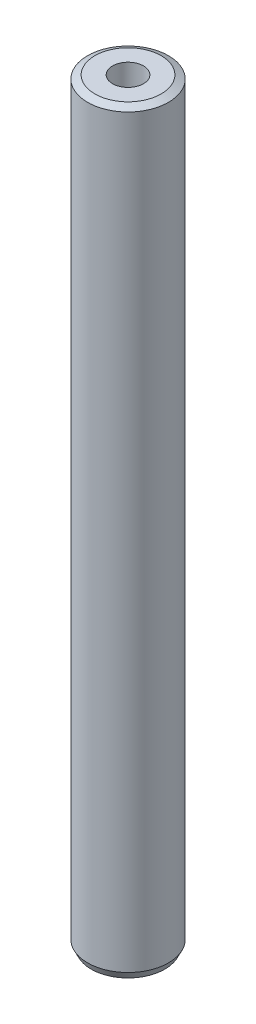
SolidWorks part; units mm, degrees
ref_plane "Front Plane" through (0, 0, 0) normal (0, 0, 1) x (1, 0, 0)
ref_plane "Top Plane" through (0, 0, 0) normal (0, 1, 0) x (1, 0, 0)
ref_plane "Right Plane" through (0, 0, 0) normal (1, 0, 0) x (0, 0, -1)
sketch "Sketch1" plane through (0, 0, 0) normal (0, 1, 0) x (1, 0, 0)
  circle A0 centre (0, 0) radius 22.5
  dimension "SHAFT_OD" = 45
extrude "Boss-Extrude1" add sketch "Sketch1" along normal blind 420.6427
sketch "Sketch2" plane through (0, 0, 0) normal (0, 1, 0) x (1, 0, 0)
  circle A0 centre (0, 0) radius 8.6047
  dimension "BORE_D" = 17.2095
extrude "Cut-Extrude1" cut sketch "Sketch2" along normal through all
chamfer "Chamfer1" distance 2.0182 angle 63.566 2 edges at (0, 420.6427, 22.5) (0, 0, 22.5) first distance on face at (0, 420.6427, 22.5) first distance on face at (0, 0, 8.6047)
